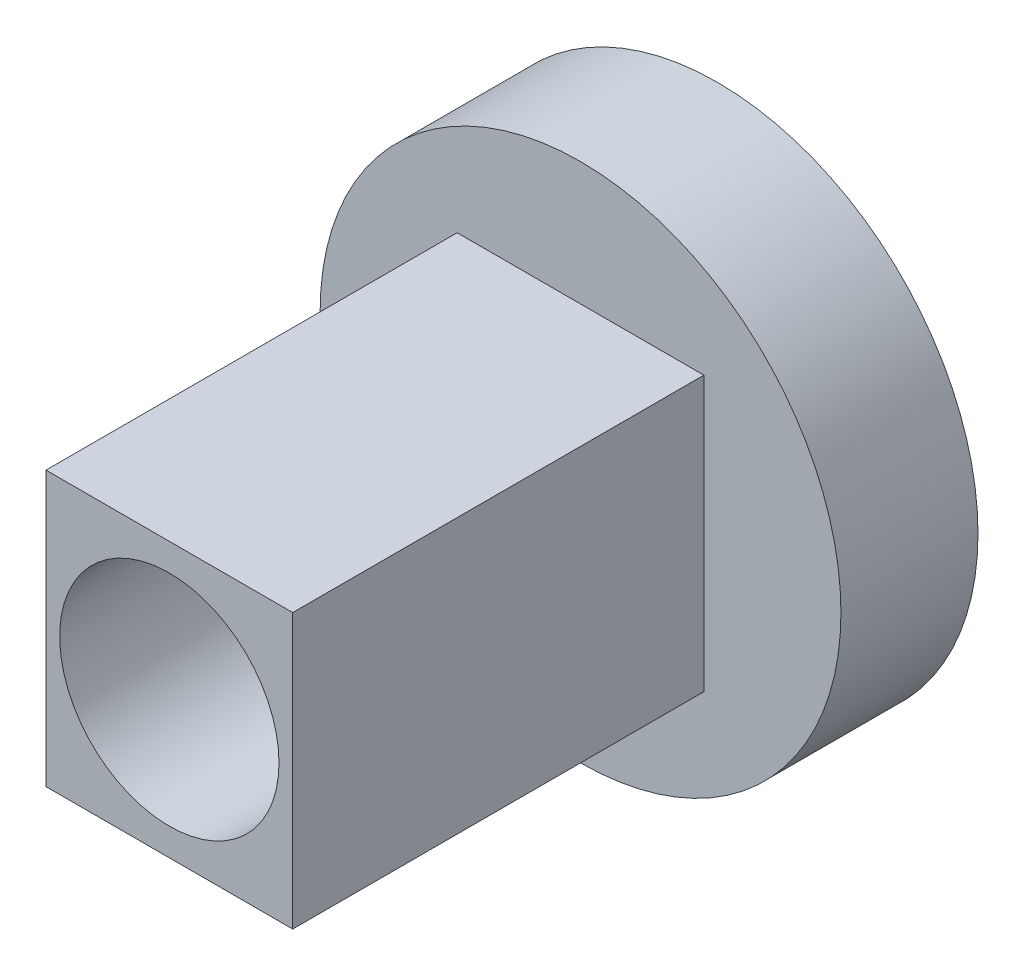
SolidWorks part; units mm, degrees
ref_plane "Спереди" through (0, 0, 0) normal (0, 0, 1) x (1, 0, 0)
ref_plane "Сверху" through (0, 0, 0) normal (0, 1, 0) x (1, 0, 0)
ref_plane "Справа" through (0, 0, 0) normal (1, 0, 0) x (0, 0, -1)
sketch "Эскиз1" plane through (0, 0, 0) normal (0, 0, 1) x (1, 0, 0)
  circle A0 centre (0, 0) radius 95
  dimension "D1" = 190
extrude "Бобышка-Вытянуть1" add sketch "Эскиз1" along normal blind 50
sketch "Эскиз2" plane through (0, 0, 50) normal (0, 0, 1) x (1, 0, 0)
  line L1 (-45, -50) -> (45, -50)
  line L2 (-45, -50) -> (-45, 50)
  line L3 (-45, 50) -> (45, 50)
  line L4 (45, -50) -> (45, 50)
  line L5 (-45, -50) -> (45, 50) construction
  line L6 (-45, 50) -> (45, -50) construction
  point P0 (0, 0)
  dimension "D1" = 90
  dimension "D2" = 100
extrude "Бобышка-Вытянуть2" add sketch "Эскиз2" along normal blind 150
sketch "Эскиз3" plane through (0, 0, 200) normal (0, 0, 1) x (1, 0, 0)
  circle A0 centre (0, 0) radius 40
  dimension "D1" = 80
extrude "Вырез-Вытянуть1" cut sketch "Эскиз3" against normal through all
shell "Оболочка1" thickness 3 removed face at (40, 0, 0)
